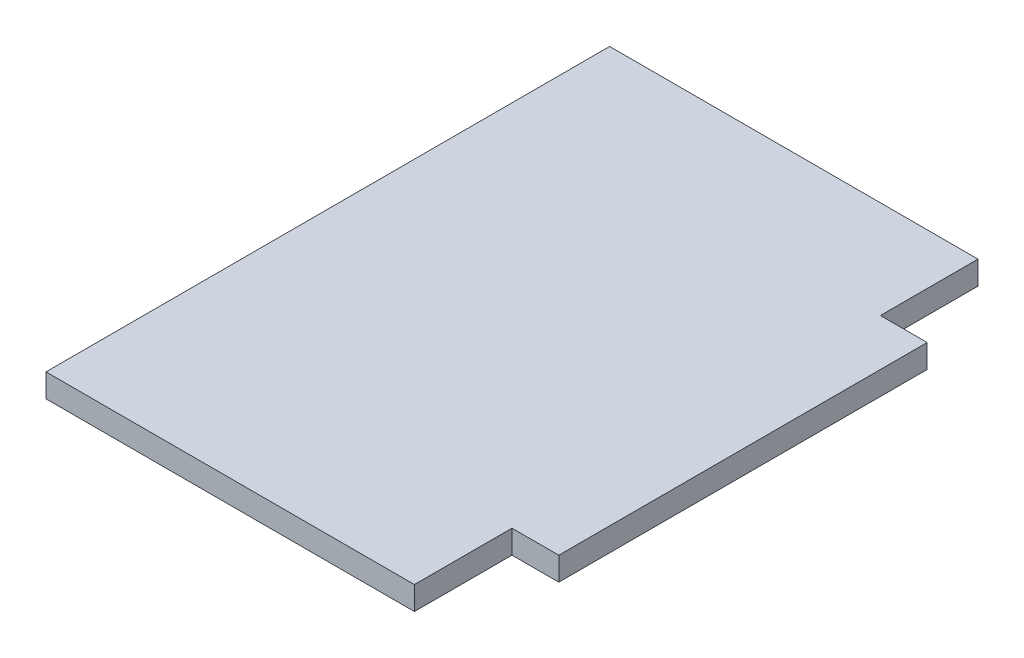
SolidWorks part; units mm, degrees
material "Cedar"
ref_plane "Front Plane" through (0, 0, 0) normal (0, 0, 1) x (1, 0, 0)
ref_plane "Top Plane" through (0, 0, 0) normal (0, 1, 0) x (1, 0, 0)
ref_plane "Right Plane" through (0, 0, 0) normal (1, 0, 0) x (0, 0, -1)
sketch "Sketch1" plane through (0, 0, 0) normal (0, 1, 0) x (1, 0, 0)
  line L0 (-25, 13.25) -> (25, 13.25)
  line L1 (25, 13.25) -> (25, 0)
  line L2 (25, 0) -> (31.35, 0)
  line L3 (31.35, 0) -> (31.35, -50)
  line L4 (31.35, -50) -> (25, -50)
  line L5 (25, -50) -> (25, -63.25)
  line L6 (25, -63.25) -> (-25, -63.25)
  line L7 (-25, -63.25) -> (-25, -50)
  line L8 (-25, -50) -> (-31.35, -50)
  line L9 (-31.35, -50) -> (-31.35, 0)
  line L10 (-31.35, 0) -> (-25, 0)
  line L11 (-25, 0) -> (-25, 13.25)
  line L12 (-25, 0) -> (-25, -50) construction
  point P11 (0, 13.25)
  point P14 (-31.35, -25)
  dimension "D1" = 6.35
  dimension "D2" = 50
  dimension "D3" = 50
  dimension "D4" = 76.5
extrude "Boss-Extrude1" add sketch "Sketch1" along normal blind 3.175 contours L11 L12 L7 L6 L5 L4 L3 L2 L1 L0 region at (2.1595, 0, 25)
equation "\"length\"= 76.5mm"
equation "\"w_mach\" = 50mm"
equation "\"w_tab\"= 50mm"
equation "\"t_wood\"= 0.125in"
equation "\"t_side\"= 0.25in"
equation "\"D1@Sketch1\"=\"t_side\""
equation "\"D2@Sketch1\"=\"w_tab\""
equation "\"D3@Sketch1\"=\"w_mach\""
equation "\"D4@Sketch1\"=\"length\""
equation "\"D1@Boss-Extrude1\"=\"t_wood\""
